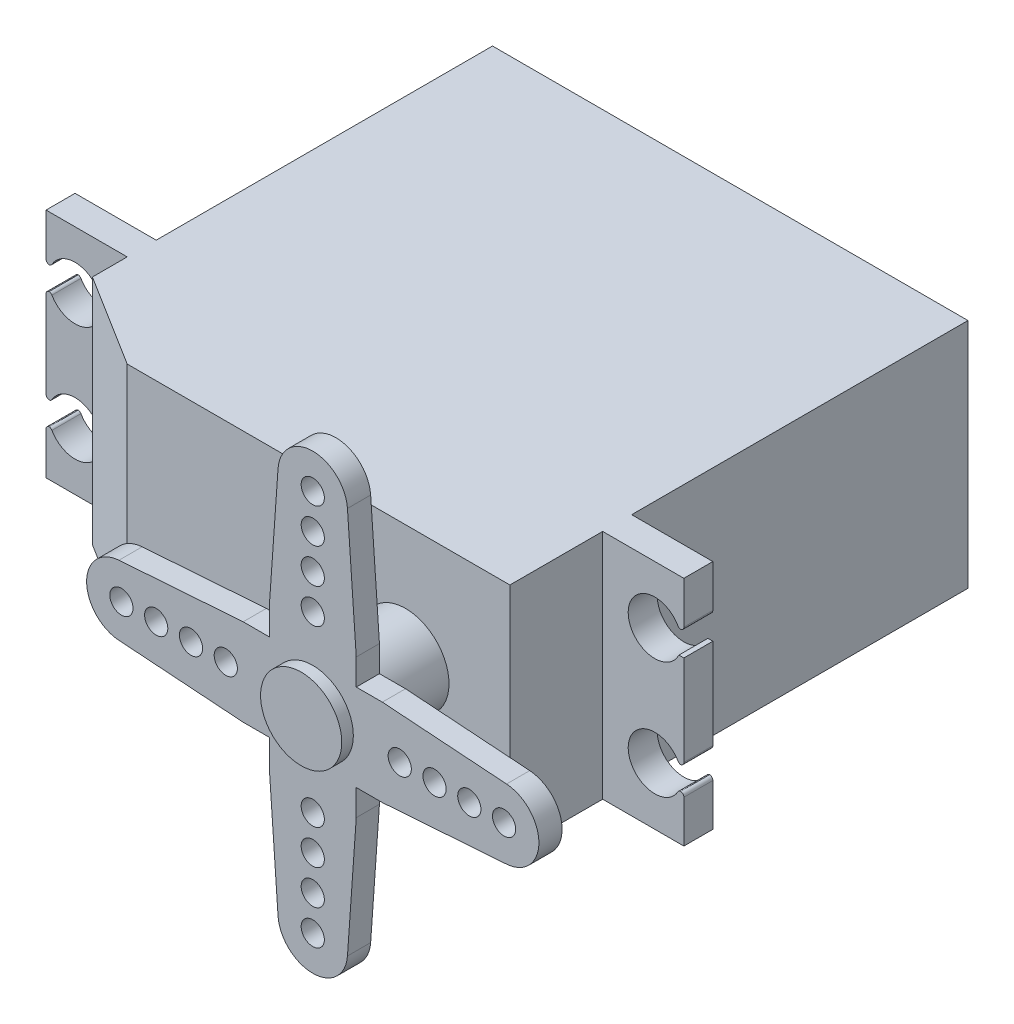
SolidWorks part; units mm, degrees
ref_plane "Front Plane" through (0, 0, 0) normal (0, 0, 1) x (1, 0, 0)
ref_plane "Top Plane" through (0, 0, 0) normal (0, 1, 0) x (1, 0, 0)
ref_plane "Right Plane" through (0, 0, 0) normal (1, 0, 0) x (0, 0, -1)
sketch "Sketch1" plane through (0, 0, 0) normal (0, 0, 1) x (1, 0, 0)
  line L1 (-20.5, 10) -> (20.5, 10)
  line L2 (-20.5, 10) -> (-20.5, -10)
  line L3 (-20.5, -10) -> (20.5, -10)
  line L4 (20.5, 10) -> (20.5, -10)
  line L5 (-20.5, 10) -> (20.5, -10) construction
  line L6 (-20.5, -10) -> (20.5, 10) construction
  point P0 (0, 0)
  dimension "D1" = 20
  dimension "D2" = 41
extrude "Boss-Extrude1" add sketch "Sketch1" along normal blind 39.5
chamfer "Chamfer1" distance 5 distance2 8 1 edges at (-20.5, 0, 39.5) first distance on face at (-20.5, 0, 19.75)
ref_plane "Plane1" through (0, 0, 31.5) normal (0, 0, 1) x (1, 0, 0)
sketch "Sketch2" plane through (0, 0, 31.5) normal (0, 0, 1) x (1, 0, 0)
  line L0 (-20.5, -10) -> (-20.5, 10) construction
  line L1 (20.5, 10) -> (27.5, 10)
  line L2 (20.5, 10) -> (20.5, -10)
  line L3 (20.5, -10) -> (27.5, -10)
  line L4 (27.5, 10) -> (27.5, -10)
  line L5 (-20.5, 10) -> (-27.5, 10)
  line L6 (-20.5, 10) -> (-20.5, -10)
  line L7 (-20.5, -10) -> (-27.5, -10)
  line L8 (-27.5, 10) -> (-27.5, -10)
  line L9 (-12.5, -10) -> (-20.5, -10) construction
  dimension "D1" = 7
  dimension "D2" = 7
extrude "Boss-Extrude2" add sketch "Sketch2" against normal blind 2.5
sketch "Sketch3" plane through (0, 0, 31.5) normal (0, 0, 1) x (1, 0, 0)
  line L0 (-25, 7.35) -> (-25, -7.35)
  line L1 (-27.0712, -6.05) -> (-27.5, -6.05)
  line L2 (-27.5, -4.05) -> (-27.5, -6.05)
  line L3 (-20.5, -10) -> (-20.5, 10) construction
  line L4 (-27.5, 6.05) -> (-27.0712, 6.05)
  line L5 (-27.5, 10) -> (-27.5, -10) construction
  line L6 (-27.5, 4.05) -> (-27.0712, 4.05)
  line L7 (-27.5, 6.05) -> (-27.5, 4.05)
  line L8 (-27.5, -4.05) -> (-27.0712, -4.05)
  arc A0 (-27.0712, 4.05) -> (-27.0712, 6.05) centre (-25, 5.05) ccw
  arc A1 (-27.0712, -6.05) -> (-27.0712, -4.05) centre (-25, -5.05) ccw
  line M3 (-27.5, 10) -> (-27.5, -10)
  dimension "D1" = 4.6
  dimension "D2" = 4.6
  dimension "D5" = 4.5
  dimension "D3" = 14.7
  dimension "D4" = 7.35
  dimension "D6" = 2
  dimension "D7" = 1
  dimension "D8" = 2
  dimension "D9" = 1
extrude "Cut-Extrude1" cut sketch "Sketch3" against normal up to next contours L0 A1 L8 L1 M3 | L0 A0 L4 L6 M3 | L0 A0 | L0 A1 region at (-24.0238, 5.05, 31.5) region at (-26.0616, 5.05, 31.5) region at (-24.0238, -5.05, 31.5) region at (-26.0616, -5.05, 31.5)
fillet "Fillet1" radius 0.3 8 edges at (-27.5, -6.05, 30.25) (-27.0712, -6.05, 30.25) (-27.5, -4.05, 30.25) (-27.0712, -4.05, 30.25) (-27.5, 6.05, 30.25) (-27.0712, 6.05, 30.25) (-27.5, 4.05, 30.25) (-27.0712, 4.05, 30.25)
mirror "Mirror1" about plane through (0, 0, 0) normal (1, 0, 0) of "Cut-Extrude1"
sketch "Sketch4" plane through (0, 0, 39.5) normal (0, 0, 1) x (1, 0, 0)
  line L0 (20.5, 10) -> (20.5, -10) construction
  circle A0 centre (11.5, 0) radius 3.75
  dimension "D1" = 7.5
  dimension "D2" = 9
extrude "Boss-Extrude3" add sketch "Sketch4" along normal blind 8
sketch "Sketch5" plane through (0, 0, 47.5) normal (0, 0, 1) x (1, 0, 0)
  line L0 (11.5, 19.5) -> (11.5, -19.5) construction
  line L1 (11.5, 3.75) -> (5.5, 3.75)
  line L2 (5.5, 3.75) -> (-5.2116, 2.9925)
  line L3 (11.5, -3.75) -> (5.5, -3.75)
  line L4 (-5.2116, -2.9925) -> (5.5, -3.75)
  line L5 (7.75, 0) -> (7.75, 6)
  line L6 (15.25, 0) -> (15.25, 6)
  line L7 (11.5, 3.75) -> (17.5, 3.75)
  line L8 (11.5, -3.75) -> (17.5, -3.75)
  line L9 (15.25, 0) -> (15.25, -6)
  line L10 (7.75, 0) -> (7.75, -6)
  line L11 (8.5075, 16.7116) -> (7.75, 6)
  line L12 (14.4925, 16.7116) -> (15.25, 6)
  line L13 (28.2116, 2.9925) -> (17.5, 3.75)
  line L14 (28.2116, -2.9925) -> (17.5, -3.75)
  line L15 (14.4925, -16.7116) -> (15.25, -6)
  line L16 (8.5075, -16.7116) -> (7.75, -6)
  circle A0 centre (11.5, 0) radius 3.75
  circle A1 centre (11.5, 16.5) radius 1
  circle A2 centre (11.5, -16.5) radius 1
  circle A3 centre (-5, 0) radius 1
  circle A4 centre (28, 0) radius 1
  arc A5 (14.4925, 16.7116) -> (8.5075, 16.7116) centre (11.5, 16.5) ccw
  arc A6 (8.5075, -16.7116) -> (14.4925, -16.7116) centre (11.5, -16.5) ccw
  arc A7 (28.2116, -2.9925) -> (28.2116, 2.9925) centre (28, 0) ccw
  arc A8 (-5.2116, 2.9925) -> (-5.2116, -2.9925) centre (-5, 0) ccw
  circle M2 centre (11.5, 0) radius 3.75
  dimension "D1" = 33
  dimension "D3" = 33
  dimension "D4" = 16.5
  dimension "D5" = 2
  dimension "D6" = 39
  dimension "D7" = 6
  dimension "D2" = 16.5
extrude "Boss-Extrude4" add sketch "Sketch5" against normal blind 2 contours A5 L0 A1 L7 L6 L12 | L0 A5 L11 L5 L1 A1 | L2 A8 L4 L3 L10 L5 L1 A3 | L14 A7 L13 L7 L6 L9 L8 A4 | L8 L0 A2 A6 L15 L9 | L0 L3 L10 L16 A6 A2 | L10 L3 M2 | L5 L1 M2 | L7 L6 M2 | L9 L8 M2 region at (9.7934, 10.7897, 47.5) region at (8.5876, 2.9124, 47.5) region at (13.2066, 10.7897, 47.5) region at (14.4124, 2.9124, 47.5) region at (13.2066, -10.7897, 47.5) region at (9.7934, -10.7897, 47.5) region at (14.4124, -2.9124, 47.5) region at (8.5876, -2.9124, 47.5) region at (0.7103, 0, 47.5) region at (22.2897, 0, 47.5)
sketch "Sketch6" plane through (0, 0, 47.5) normal (0, 0, 1) x (1, 0, 0)
  circle A0 centre (11.5, 0) radius 3.5
  dimension "D1" = 7
extrude "Boss-Extrude5" add sketch "Sketch6" along normal blind 1
fillet "Fillet2" radius 0.3 6 edges at (27.0712, -6.05, 30.25) (27.5, -6.05, 30.25) (27.0712, -4.05, 30.25) (27.5, -4.05, 30.25) (27.5, 6.05, 30.25) (27.0712, 6.05, 30.25)
sketch "Sketch7" plane through (0, 0, 47.5) normal (0, 0, 1) x (1, 0, 0)
  line L0 (11.5, 13.5) -> (11.5, 0) construction
  line L1 (11.5, 0) -> (25, 0) construction
  line L2 (11.5, 0) -> (11.5, -13.5) construction
  line L3 (11.5, 0) -> (-2, 0) construction
  circle A0 centre (11.5, 13.5) radius 1
  circle A1 centre (11.5, 10.5) radius 1
  circle A2 centre (11.5, 7.5) radius 1
  circle A3 centre (25, 0) radius 1
  circle A4 centre (22, 0) radius 1
  circle A5 centre (19, 0) radius 1
  circle A6 centre (11.5, -7.5) radius 1
  circle A7 centre (11.5, -10.5) radius 1
  circle A8 centre (11.5, -13.5) radius 1
  circle A9 centre (-2, 0) radius 1
  circle A10 centre (1, 0) radius 1
  circle A11 centre (4, 0) radius 1
  circle A12 centre (11.5, 16.5) radius 1 construction
  circle A13 centre (28, 0) radius 1 construction
  circle A14 centre (11.5, -16.5) radius 1 construction
  circle A15 centre (-5, 0) radius 1 construction
  dimension "D1" = 2
  dimension "D2" = 3
  dimension "D3" = 3
  dimension "D4" = 3
  dimension "D5" = 3
  dimension "D6" = 2
  dimension "D7" = 3
  dimension "D8" = 3
  dimension "D9" = 3
  dimension "D10" = 3
  dimension "D11" = 3
  dimension "D12" = 3
  dimension "D13" = 3
  dimension "D14" = 3
extrude "Cut-Extrude2" cut sketch "Sketch7" against normal up to next
